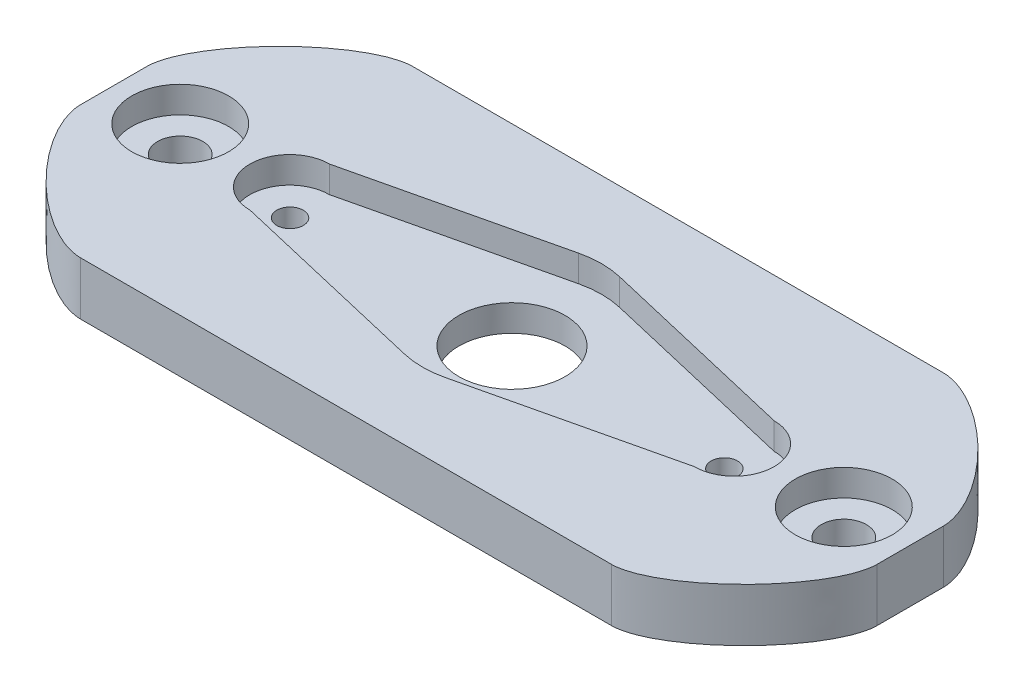
SolidWorks part; units mm, degrees
ref_plane "Front Plane" through (0, 0, 0) normal (0, 0, 1) x (1, 0, 0)
ref_plane "Top Plane" through (0, 0, 0) normal (0, 1, 0) x (1, 0, 0)
ref_plane "Right Plane" through (0, 0, 0) normal (1, 0, 0) x (0, 0, -1)
sketch "Sketch1" plane through (0, 0, 0) normal (0, 0, 1) x (1, 0, 0)
  line L1 (-20.0715, -2.0352) -> (39.9285, -2.0352)
  line L2 (-20.0715, -2.0352) -> (-20.0715, -10.0352)
  line L3 (-20.0715, -10.0352) -> (39.9285, -10.0352)
  line L4 (39.9285, -2.0352) -> (39.9285, -10.0352)
extrude "Boss-Extrude1" add sketch "Sketch1" along normal blind 25
sketch "Sketch2" plane through (0, 0, 25) normal (0, 0, 1) x (1, 0, 0)
  line L0 (-20.0715, -6.0352) -> (-20.0715, -8.0352)
  line L1 (-20.0715, -2.0352) -> (-20.0715, -10.0352) construction
  line L2 (-20.0715, -8.0352) -> (39.9285, -8.0352)
  line L3 (39.9285, -10.0352) -> (39.9285, -2.0352) construction
  line L4 (39.9285, -8.0352) -> (39.9285, -6.0352)
  line L5 (39.9285, -6.0352) -> (-20.0715, -6.0352)
extrude "Cut-Extrude1" cut sketch "Sketch2" against normal blind 22
sketch "Sketch3" plane through (0, -2.0352, 0) normal (0, 1, 0) x (1, 0, 0)
  line L3 (26.6785, -9.5) -> (11.4717, -5.9288)
  line L4 (-6.8215, -9.5) -> (8.3853, -5.9288)
  line L5 (-6.8215, -15.5) -> (8.3853, -19.0712)
  line L6 (26.6785, -15.5) -> (11.4717, -19.0712)
  arc A0 (8.3853, -19.0712) -> (11.4717, -19.0712) centre (9.9285, -12.5) ccw
  arc A1 (-6.8215, -9.5) -> (-6.8215, -15.5) centre (-6.8215, -12.5) ccw
  arc A2 (26.6785, -15.5) -> (26.6785, -9.5) centre (26.6785, -12.5) ccw
  arc A3 (11.4717, -5.9288) -> (8.3853, -5.9288) centre (9.9285, -12.5) ccw
extrude "Cut-Extrude2" cut sketch "Sketch3" against normal blind 2
sketch "Sketch4" plane through (0, -4.0352, 0) normal (0, 1, 0) x (1, 0, 0)
  circle A0 centre (-6.7969, -12.5) radius 1
  circle A2 centre (9.9285, -12.5) radius 4
  circle A3 centre (25.9285, -12.5) radius 1
extrude "Cut-Extrude3" cut sketch "Sketch4" against normal blind 2.5
sketch "Sketch5" plane through (0, -2.0352, 0) normal (0, 1, 0) x (1, 0, 0)
  line L0 (-20.0715, -12.5) -> (-15.0715, -12.5)
  line L1 (-20.0715, -25) -> (-20.0715, 0) construction
  line L2 (-15.0715, -12.5) -> (-15.0715, 0)
  line L3 (39.9285, 0) -> (-20.0715, 0) construction
  line L4 (-15.0715, -12.5) -> (34.9285, -12.5)
  circle A0 centre (34.9285, -12.5) radius 1.7
  circle A1 centre (-15.0715, -12.5) radius 1.7
extrude "Cut-Extrude4" cut sketch "Sketch5" against normal blind 9
fillet "Fillet2" radius 10 6 edges at (-20.0715, -4.0352, 25) (-20.0715, -9.0352, 25) (39.9285, -4.0352, 25) (39.9285, -9.0352, 25) (39.9285, -6.0352, 0) (-20.0715, -6.0352, 0)
sketch "Sketch6" plane through (0, -8.0352, 0) normal (0, 1, 0) x (1, 0, 0)
  circle A0 centre (9.9285, -12.5) radius 3
extrude "Cut-Extrude5" cut sketch "Sketch6" against normal blind 4.5
sketch "Sketch7" plane through (0, -10.0352, 0) normal (0, -1, 0) x (-1, 0, 0)
  line L1 (-35.6839, -9.2377) -> (-38.1315, -11.523)
  line L2 (-38.1315, -11.523) -> (-37.3761, -14.7853)
  line L3 (-37.3761, -14.7853) -> (-34.1731, -15.7623)
  line L4 (-34.1731, -15.7623) -> (-31.7256, -13.477)
  line L5 (-31.7256, -13.477) -> (-32.4809, -10.2147)
  line L6 (-32.4809, -10.2147) -> (-35.6839, -9.2377)
  line L7 (12.1057, -10.9453) -> (12.2421, -14.2911)
  line L8 (12.2421, -14.2911) -> (15.208, -15.8458)
  line L9 (15.208, -15.8458) -> (18.0373, -14.0547)
  line L10 (18.0373, -14.0547) -> (17.9008, -10.7089)
  line L11 (17.9008, -10.7089) -> (14.935, -9.1542)
  line L12 (14.935, -9.1542) -> (12.1057, -10.9453)
  circle A0 centre (-34.9285, -12.5) radius 2.9 construction
  circle A1 centre (15.0715, -12.5) radius 2.9 construction
extrude "Cut-Extrude6" cut sketch "Sketch7" against normal blind 1
sketch "Sketch8" plane through (0, -2.0352, 0) normal (0, 1, 0) x (1, 0, 0)
  circle A0 centre (-15.0715, -12.5) radius 3.65
  circle A1 centre (34.9285, -12.5) radius 3.65
extrude "Cut-Extrude7" cut sketch "Sketch8" against normal blind 2
sketch "Sketch10" plane through (-20.0715, 0, 0) normal (-1, 0, 0) x (0, 0, 1)
  line L0 (15, -10.0352) -> (10, -10.0352) construction
  line L1 (50, -10.0352) -> (0, -10.0352)
  line L2 (50, -10.0352) -> (50, -6.0352)
  line L3 (50, -6.0352) -> (0, -6.0352)
  line L4 (0, -10.0352) -> (0, -6.0352)
extrude "Cut-Extrude8" cut sketch "Sketch10" against normal blind 61
